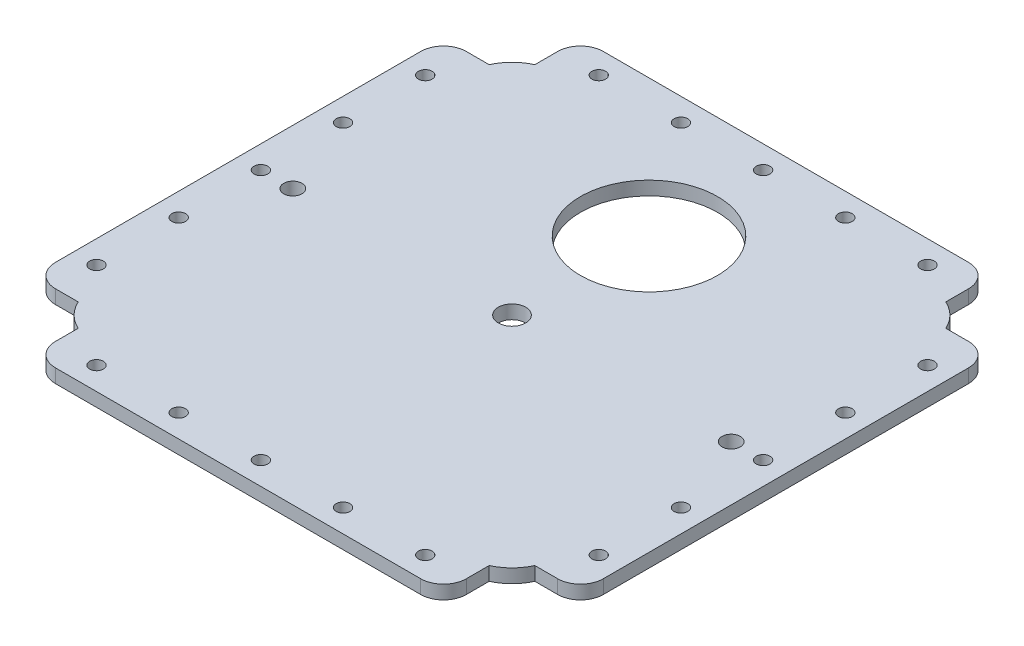
SolidWorks part; units mm, degrees
material "Polywood"
ref_plane "Спереди" through (0, 0, 0) normal (0, 0, 1) x (1, 0, 0)
ref_plane "Сверху" through (0, 0, 0) normal (0, 1, 0) x (1, 0, 0)
ref_plane "Справа" through (0, 0, 0) normal (1, 0, 0) x (0, 0, -1)
sketch "Эскиз1" plane through (0, 0, 0) normal (0, 1, 0) x (1, 0, 0)
  line L0 (0, 0) -> (0, 50000) construction
  line L1 (60, -60) -> (-60, -60)
  line L2 (60, -60) -> (60, 60)
  line L3 (60, 60) -> (-60, 60)
  line L4 (-60, -60) -> (-60, 60)
  line L5 (60, -60) -> (-60, 60) construction
  line L6 (60, 60) -> (-60, -60) construction
  line L7 (0, 0) -> (50000, 0) construction
  circle A29 centre (0, 0) radius 3
  circle A30 centre (-48, 0) radius 2
  circle A31 centre (48, 0) radius 2
  circle A32 centre (0, 30) radius 15
  point P0 (0, 0)
  dimension "D3" = 6
  dimension "D4" = 4
  dimension "D5" = 48
  dimension "D6" = 30
  dimension "D1" = 120
  dimension "D2" = 120
  dimension "D7" = 30
extrude "Бобышка-Вытянуть1" add sketch "Эскиз1" along normal blind 3
sketch "Эскиз2" plane through (0, 0, 0) normal (0, 0, 1) x (1, 0, 0)
  line L0 (0, 0) -> (0, 41.9945) construction
sketch "Эскиз3" plane through (0, 3, 0) normal (0, 1, 0) x (1, 0, 0)
  line L0 (-60, 60) -> (-45, 60)
  line L1 (60, 60) -> (-60, 60) construction
  line L2 (-45, 60) -> (-45, 50)
  line L3 (-45, 50) -> (-50, 50)
  line L4 (-50, 50) -> (-50, 45)
  line L5 (-50, 45) -> (-60, 45)
  line L6 (-60, 60) -> (-60, -60) construction
  line L7 (-60, 45) -> (-60, 60)
  line L8 (0, 0) -> (0, -50000) construction
  line L9 (0, 0) -> (50000, 0) construction
  line L10 (60, 45) -> (60, 60)
  line L11 (50, 45) -> (60, 45)
  line L12 (50, 50) -> (50, 45)
  line L13 (45, 50) -> (50, 50)
  line L14 (45, 60) -> (45, 50)
  line L15 (60, 60) -> (45, 60)
  line L16 (60, -60) -> (45, -60)
  line L17 (45, -60) -> (45, -50)
  line L18 (45, -50) -> (50, -50)
  line L19 (50, -50) -> (50, -45)
  line L20 (50, -45) -> (60, -45)
  line L21 (60, -45) -> (60, -60)
  line L22 (-60, -45) -> (-60, -60)
  line L23 (-50, -45) -> (-60, -45)
  line L24 (-50, -50) -> (-50, -45)
  line L25 (-45, -50) -> (-50, -50)
  line L26 (-45, -60) -> (-45, -50)
  line L27 (-60, -60) -> (-45, -60)
  dimension "D1" = 10
  dimension "D2" = 10
  dimension "D4" = 15
extrude "Вырез-Вытянуть1" cut sketch "Эскиз3" against normal through all
fillet "Скругление1" radius 10 4 edges at (50, 1.5, -50) (50, 1.5, 50) (-50, 1.5, 50) (-50, 1.5, -50)
fillet "Скругление2" radius 5 8 edges at (-60, 1.5, -45) (-45, 1.5, -60) (-60, 1.5, 45) (-45, 1.5, 60) (45, 1.5, 60) (60, 1.5, 45) (60, 1.5, -45) (45, 1.5, -60)
sketch "Эскиз4" plane through (0, 3, 0) normal (0, 1, 0) x (1, 0, 0)
  line L0 (40, 60) -> (-40, 60) construction
  circle A0 centre (0, 55) radius 1.5
  circle A78 centre (18, 55) radius 1.5
  circle A79 centre (36, 55) radius 1.5
  circle A80 centre (-18, 55) radius 1.5
  circle A81 centre (-36, 55) radius 1.5
  circle A82 centre (55, 0) radius 1.5
  circle A83 centre (55, -18) radius 1.5
  circle A84 centre (55, -36) radius 1.5
  circle A85 centre (55, 18) radius 1.5
  circle A86 centre (55, 36) radius 1.5
  circle A87 centre (0, -55) radius 1.5
  circle A88 centre (-18, -55) radius 1.5
  circle A89 centre (-36, -55) radius 1.5
  circle A90 centre (18, -55) radius 1.5
  circle A91 centre (36, -55) radius 1.5
  circle A92 centre (-55, 0) radius 1.5
  circle A93 centre (-55, 18) radius 1.5
  circle A94 centre (-55, 36) radius 1.5
  circle A95 centre (-55, -18) radius 1.5
  circle A96 centre (-55, -36) radius 1.5
  dimension "D1" = 3
  dimension "D2" = 5
  dimension "D3" = 3
  dimension "D4" = 3
  dimension "D5" = 4
extrude "Вырез-Вытянуть2" cut sketch "Эскиз4" against normal through all
equation "\"camera plate width\"=220"
equation "\"camera plate length\"=220"
